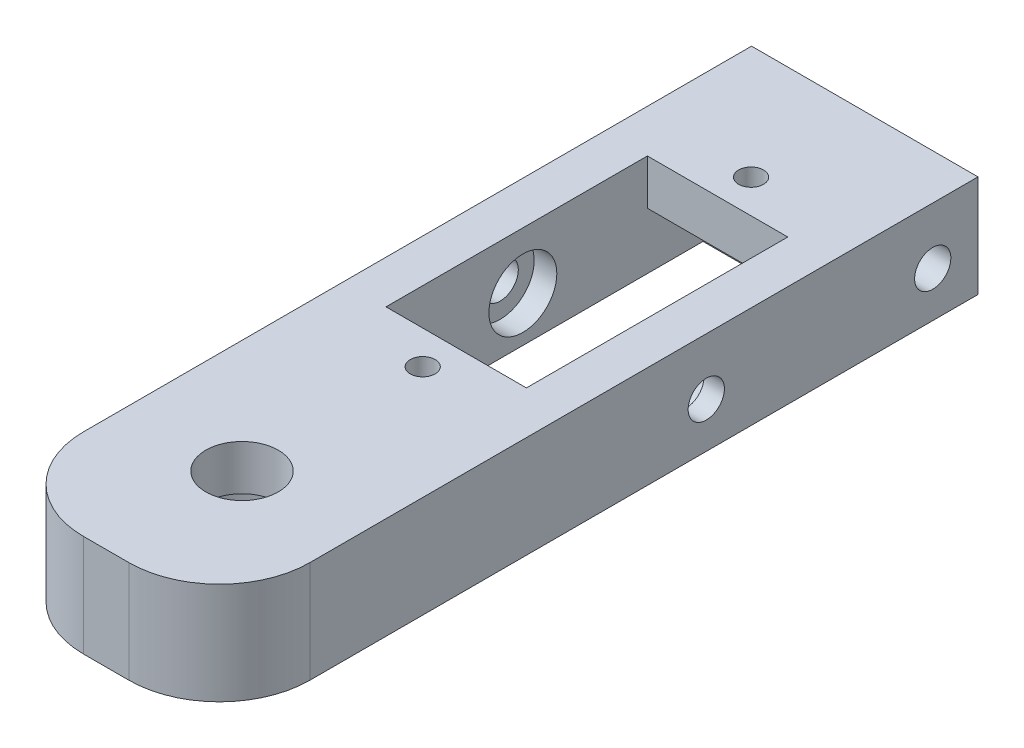
SolidWorks part; units mm, degrees
ref_plane "前视基准面" through (0, 0, 0) normal (0, 0, 1) x (1, 0, 0)
ref_plane "上视基准面" through (0, 0, 0) normal (0, 1, 0) x (1, 0, 0)
ref_plane "右视基准面" through (0, 0, 0) normal (1, 0, 0) x (0, 0, -1)
sketch "草图1" plane through (0, 0, 0) normal (1, 0, 0) x (0, 0, -1)
  line L1 (55, -4) -> (-12, -4)
  line L2 (55, -4) -> (55, 5)
  line L3 (55, 5) -> (-12, 5)
  line L4 (-12, -4) -> (-12, 5)
  line L5 (55, -4) -> (-12, 5) construction
  line L6 (55, 5) -> (-12, -4) construction
  point P0 (21.5, 0.5)
extrude "凸台-拉伸1" add sketch "草图1" along normal mid plane 20
sketch "草图2" plane through (0, -4, 0) normal (0, 1, 0) x (1, 0, 0)
  circle A0 centre (0, 0) radius 6.7
extrude "切除-拉伸1" cut sketch "草图2" along normal blind 5
sketch "草图4" plane through (0, 1, 0) normal (0, -1, 0) x (1, 0, 0)
  circle A0 centre (0, 0) radius 3.2
extrude "切除-拉伸3" cut sketch "草图4" against normal through all
sketch "草图3" plane through (0, 5, 0) normal (0, 1, 0) x (1, 0, 0)
  line L1 (6.2, 42) -> (-6.2, 42)
  line L2 (6.2, 42) -> (6.2, 18.9147)
  line L3 (6.2, 18.9147) -> (-6.2, 18.9147)
  line L4 (-6.2, 42) -> (-6.2, 18.9147)
  line L5 (6.2, 42) -> (-6.2, 18.9147) construction
  line L6 (6.2, 18.9147) -> (-6.2, 42) construction
  point P0 (0, 30.4574)
extrude "切除-拉伸2" cut sketch "草图3" against normal through all
sketch "草图5" plane through (0, -4, 0) normal (0, -1, 0) x (1, 0, 0)
  line L1 (6.2, -46.9147) -> (-6.2, -46.9147)
  line L2 (6.2, -46.9147) -> (6.2, -14)
  line L3 (6.2, -14) -> (-6.2, -14)
  line L4 (-6.2, -46.9147) -> (-6.2, -14)
  line L5 (6.2, -46.9147) -> (-6.2, -14) construction
  line L6 (6.2, -14) -> (-6.2, -46.9147) construction
  line L7 (-6.2, -42) -> (-6.2, -18.9147) construction
  line L8 (-6.2, -18.9147) -> (6.2, -18.9147) construction
  point P0 (0, -30.4574)
  point P8 (-6.2, -30.4574)
  point P11 (0, -18.9147)
extrude "切除-拉伸4" cut sketch "草图5" against normal offset from surface (5 mm away) 4 up to face at (0, 5, -30.4574)
sketch "草图6" plane through (0, 1, 0) normal (0, -1, 0) x (1, 0, 0)
  line L0 (-6.2, -30.4574) -> (6.2, -30.4574) construction
  line L1 (-6.2, -46.9147) -> (-6.2, -14) construction
  line L2 (6.2, -14) -> (6.2, -46.9147) construction
  line L3 (0, -30.4574) -> (0, -15.9574) construction
  circle A0 centre (0, -15.9574) radius 1.1
  circle A2 centre (0, -44.9574) radius 1.1
extrude "切除-拉伸5" cut sketch "草图6" against normal through all
fillet "圆角1" radius 8 2 edges at (-10, 0.5, 12) (10, 0.5, 12)
sketch "草图7" plane through (10, 0, 0) normal (1, 0, 0) x (0, 0, -1)
  line L0 (31.0016, 0) -> (51.0016, 0) construction
  circle A0 centre (51.0016, 0) radius 1.6
  circle A1 centre (31.0016, 0) radius 1.6
extrude "切除-拉伸6" cut sketch "草图7" against normal through all
sketch "草图8" plane through (-6.2, 0, 0) normal (1, 0, 0) x (0, 0, -1)
  circle A0 centre (31.0016, 0) radius 3
extrude "切除-拉伸7" cut sketch "草图8" against normal blind 2
mirror "镜向1" about plane through (0, 0, 0) normal (1, 0, 0) of "切除-拉伸7"
